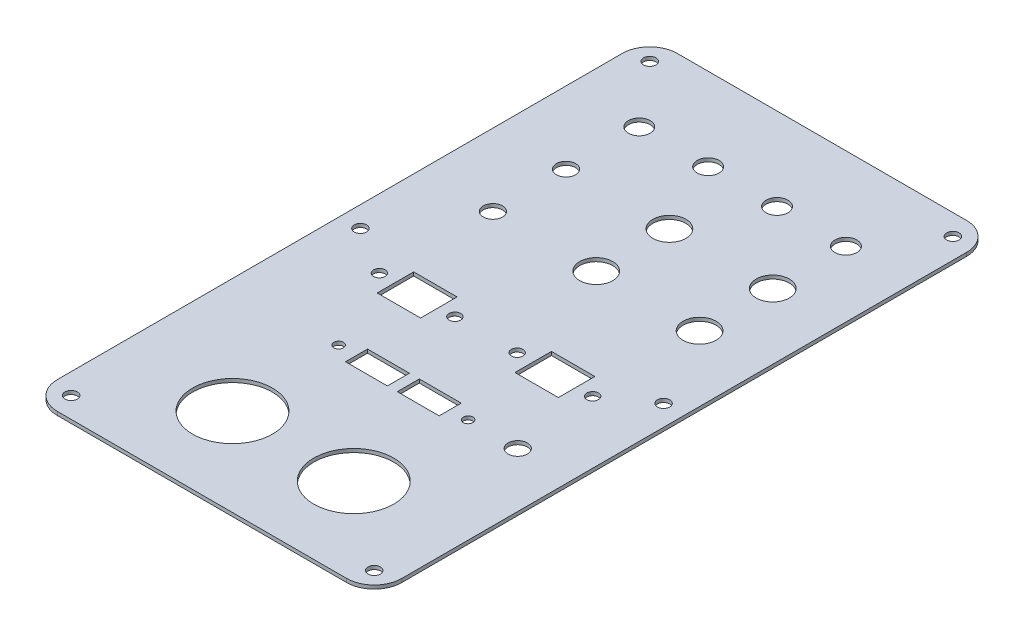
SolidWorks part; units mm, degrees
note: The reader was unsure of these and kept them because the rebuilt part matched: thickness of "Base-Flange1", "Sheet-Metal1", "Sheet-Metal2", "Sheet-Metal3", "Sheet-Metal4", "Sheet-Metal5".
material "5052-H32"
ref_plane "Front Plane" through (0, 0, 0) normal (0, 0, 1) x (1, 0, 0)
ref_plane "Top Plane" through (0, 0, 0) normal (0, 1, 0) x (1, 0, 0)
ref_plane "Right Plane" through (0, 0, 0) normal (1, 0, 0) x (0, 0, -1)
sketch "Sketch1" plane through (0, 0, 0) normal (0, 1, 0) x (1, 0, 0)
  line L0 (53.8121, -94.3814) -> (-56.1879, 115.6186) construction
  line L1 (-63.6879, 123.1186) -> (61.3121, 123.1186)
  line L2 (-63.6879, 123.1186) -> (-63.6879, -101.8814)
  line L3 (-63.6879, -101.8814) -> (61.3121, -101.8814)
  line L4 (61.3121, 123.1186) -> (61.3121, -101.8814)
  line L5 (-63.6879, 123.1186) -> (61.3121, -101.8814) construction
  line L6 (-63.6879, -101.8814) -> (61.3121, 123.1186) construction
  point P0 (-1.1879, 10.6186)
  point P10 (-1.1879, 10.6186)
  dimension "D1" = 225
  dimension "D2" = 125
base flange "Base-Flange1" sketch "Sketch1" thickness 1.3 reverse thickness direction no parameters "D1"=1.016
sketch "Sketch6" plane through (0, 0, 0) normal (0, 1, 0) x (1, 0, 0)
  circle A0 centre (53.8121, 115.6186) radius 2.25
  circle A1 centre (53.8121, -94.3814) radius 2.25
  circle A2 centre (-56.1879, -94.3814) radius 2.25
  circle A3 centre (-56.1879, 115.6186) radius 2.25
  circle A4 centre (53.8121, 10.6186) radius 2.25
  circle A5 centre (-56.1879, 10.6186) radius 2.25
  dimension "D1" = 4.5
extrude "Cut-Extrude1" cut sketch "Sketch6" against normal blind 10 normal cut yes
fillet "Fillet1" radius 10 4 edges at (-63.6879, -0.65, -123.1186) (61.3121, -0.65, -123.1186) (-63.6879, -0.65, 101.8814) (61.3121, -0.65, 101.8814)
sketch "Sketch7" plane through (0, 0, 0) normal (0, 1, 0) x (1, 0, 0)
  line L0 (23.5, -30) -> (-23.5, -30) construction
  line L1 (-1.8, -26) -> (1.8, -26) construction
  line L2 (17, -26) -> (1.8, -26)
  line L3 (17, -26) -> (17, -34)
  line L4 (17, -34) -> (1.8, -34)
  line L5 (1.8, -26) -> (1.8, -34)
  line L6 (17, -26) -> (1.8, -34) construction
  line L7 (17, -34) -> (1.8, -26) construction
  line L8 (-17, -26) -> (-1.8, -26)
  line L9 (-17, -26) -> (-17, -34)
  line L10 (-17, -34) -> (-1.8, -34)
  line L11 (-1.8, -26) -> (-1.8, -34)
  line L12 (-17, -26) -> (-1.8, -34) construction
  line L13 (-17, -34) -> (-1.8, -26) construction
  line L14 (23.5, -30) -> (-23.5, -30) construction
  line L15 (23.5, -35.75) -> (-23.5, -35.75) construction
  line L16 (23.5, -24.25) -> (-23.5, -24.25) construction
  line L17 (0, 0) -> (0, 123.1186) construction
  line L18 (51.3121, 123.1186) -> (-53.6879, 123.1186) construction
  line L19 (17.125, -6.625) -> (32.875, 6.625) construction
  line L20 (17.125, 6.625) -> (32.875, -6.625) construction
  line L21 (38.7, 0) -> (11.3, 0) construction
  line L22 (32.875, 6.625) -> (32.875, -6.625)
  line L23 (17.125, -6.625) -> (32.875, -6.625)
  line L24 (17.125, 6.625) -> (17.125, -6.625)
  line L25 (17.125, 6.625) -> (32.875, 6.625)
  line L34 (-38.7, 0) -> (-11.3, 0) construction
  line L35 (-17.125, 6.625) -> (-32.875, 6.625)
  line L36 (-17.125, 6.625) -> (-17.125, -6.625)
  line L37 (-17.125, -6.625) -> (-32.875, -6.625)
  line L38 (-32.875, 6.625) -> (-32.875, -6.625)
  line L39 (-17.125, 6.625) -> (-32.875, -6.625) construction
  line L40 (-17.125, -6.625) -> (-32.875, 6.625) construction
  circle A0 centre (22, -70) radius 14.5
  circle A1 centre (-22, -70) radius 14.5
  circle A2 centre (22, -70) radius 21 construction
  circle A3 centre (-22, -70) radius 21 construction
  circle A4 centre (23.5, -30) radius 1.75
  circle A5 centre (-23.5, -30) radius 1.75
  arc A6 (23.5, -35.75) -> (23.5, -24.25) centre (23.5, -30) ccw construction
  arc A7 (-23.5, -24.25) -> (-23.5, -35.75) centre (-23.5, -30) ccw construction
  circle A8 centre (11.3, 0) radius 2.1
  circle A9 centre (38.7, 0) radius 2.1
  circle A10 centre (-12.5, 93.1186) radius 3.9688
  circle A11 centre (-37.5, 93.1186) radius 3.9687
  circle A12 centre (-38.7, 0) radius 2.1
  circle A13 centre (-11.3, 0) radius 2.1
  circle A14 centre (37.5, 93.1186) radius 3.9687
  circle A15 centre (12.5, 93.1186) radius 3.9688
  point P11 (0, -30)
  point P12 (9.4, -30)
  point P17 (-9.4, -30)
  point P22 (0, -26)
  point P24 (0, -30)
  point P33 (0, 0)
  point P42 (25, 0)
  point P47 (0, 93.1186)
  point P51 (-25, 0)
  dimension "D1" = 29
  dimension "D5" = 42
  dimension "D6" = 3.5
  dimension "D21" = 4.2
  dimension "D14" = 7.9375
  dimension "D2" = 70
  dimension "D3" = 22
  dimension "D4" = 22
  dimension "D7" = 30
  dimension "D8" = 47
  dimension "D9" = 8
  dimension "D10" = 15.2
  dimension "D11" = 34
  dimension "D12" = 11.5
  dimension "D13" = 25
  dimension "D15" = 12.5
  dimension "D16" = 25
  dimension "D17" = 30
  dimension "D19" = 15.75
  dimension "D20" = 13.25
  dimension "D22" = 27.4
extrude "Cut-Extrude2" cut sketch "Sketch7" against normal blind 10 normal cut yes
sketch "Sketch8" plane through (0, 0, 0) normal (0, 1, 0) x (1, 0, 0)
  line L0 (-37.5, 93.1186) -> (-37.5, 40) construction
  circle A0 centre (-37.5, 66.5593) radius 3.5
  circle A1 centre (-37.5, 40) radius 3.5
  circle A2 centre (41.5, -30) radius 3.5
  circle A3 centre (23.5, -30) radius 1.75 construction
  point P4 (-37.5, 93.1186)
  point P12 (23.5, -30)
  dimension "D1" = 7
  dimension "D2" = 18
  dimension "D3" = 40
extrude "Cut-Extrude3" cut sketch "Sketch8" against normal blind 10 normal cut yes
sketch "Sketch9" plane through (0, 0, 0) normal (0, 1, 0) x (1, 0, 0)
  line L1 (-37.5, 40) -> (37.5, 40) construction
  circle A0 centre (37.5, 40) radius 6
  circle A1 centre (37.5, 66.5593) radius 6
  circle A2 centre (0, 66.5593) radius 6
  circle A3 centre (0, 40) radius 6
  point P2 (-37.5, 40)
  point P6 (-37.5, 66.5593)
  dimension "D1" = 12
extrude "Cut-Extrude4" cut sketch "Sketch9" against normal blind 10 normal cut yes
sketch "Bend-Lines1" [suppressed] plane through (0, 0, 0) normal (0, 1, 0) x (1, 0, 0)
sketch "Bounding-Box1" [suppressed] plane through (0, 0, 0) normal (0, 1, 0) x (1, 0, 0)
sheet metal parameters "Sheet-Metal1" thickness 1.3 parameters "D1"=1.016, "D7"=1.52
flat pattern "Flat-Pattern1" [suppressed]
sketch "Bend-Lines2" plane through (0, 0, 0) normal (0, 1, 0) x (1, 0, 0)
sketch "Bounding-Box2" [suppressed] plane through (0, 0, 0) normal (0, 1, 0) x (1, 0, 0)
sheet metal parameters "Sheet-Metal2" thickness 1.3 parameters "D1"=1.016, "D7"=1.52
flat pattern "Flat-Pattern1"
sketch "Bend-Lines2" plane through (0, 0, 0) normal (0, 1, 0) x (1, 0, 0)
sketch "Bounding-Box2" [suppressed] plane through (0, 0, 0) normal (0, 1, 0) x (1, 0, 0)
sheet metal parameters "Sheet-Metal3" thickness 1.3 parameters "D1"=1.016, "D7"=1.52
flat pattern "Flat-Pattern1"
sketch "Bend-Lines2" plane through (0, 0, 0) normal (0, 1, 0) x (1, 0, 0)
sketch3d "Bounding-Box2" [suppressed]
  line L0 (-63.6879, 111.8836, 0) -> (-63.6879, -113.1164, 0) construction
  line L1 (61.3121, 111.8836, 0) -> (61.3121, -113.1164, 0) construction
  line L2 (-63.6879, 111.8836, 0) -> (61.3121, 111.8836, 0) construction
  line L3 (-63.6879, -113.1164, 0) -> (61.3121, -113.1164, 0) construction
sheet metal parameters "Sheet-Metal4" thickness 1.3 parameters "D1"=1.016, "D7"=1.52
flat pattern "Flat-Pattern1"
sketch "Bend-Lines2" plane through (0, 0, 0) normal (0, 1, 0) x (1, 0, 0)
sketch3d "Bounding-Box2" [suppressed]
  line L0 (-63.6879, 111.8836, 0) -> (-63.6879, -113.1164, 0) construction
  line L1 (61.3121, 111.8836, 0) -> (61.3121, -113.1164, 0) construction
  line L2 (-63.6879, 111.8836, 0) -> (61.3121, 111.8836, 0) construction
  line L3 (-63.6879, -113.1164, 0) -> (61.3121, -113.1164, 0) construction
sheet metal parameters "Sheet-Metal5" thickness 1.3 parameters "D1"=1.016, "D7"=1.52
flat pattern "Flat-Pattern1"
sketch "Bend-Lines2" plane through (0, 0, 0) normal (0, 1, 0) x (1, 0, 0)
sketch3d "Bounding-Box2" [suppressed]
  line L0 (-63.6879, 111.8836, 0) -> (-63.6879, -113.1164, 0) construction
  line L1 (61.3121, 111.8836, 0) -> (61.3121, -113.1164, 0) construction
  line L2 (-63.6879, 111.8836, 0) -> (61.3121, 111.8836, 0) construction
  line L3 (-63.6879, -113.1164, 0) -> (61.3121, -113.1164, 0) construction
